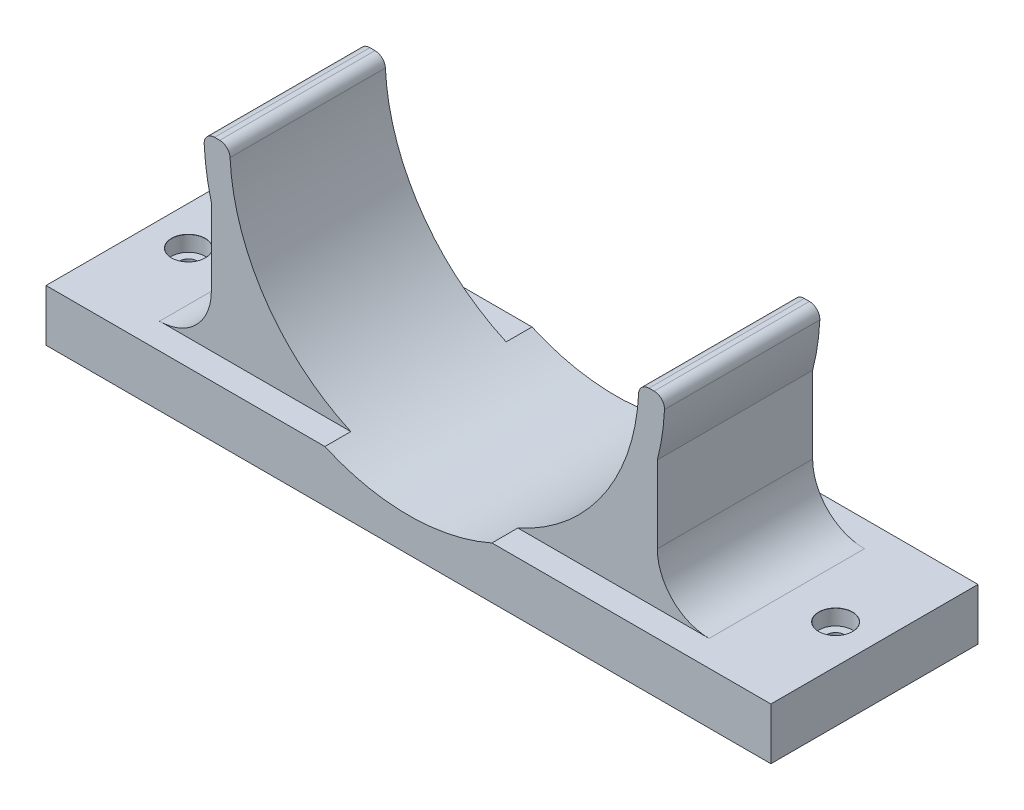
SolidWorks part; units mm, degrees
ref_plane "Front Plane" through (0, 0, 0) normal (0, 0, 1) x (1, 0, 0)
ref_plane "Top Plane" through (0, 0, 0) normal (0, 1, 0) x (1, 0, 0)
ref_plane "Right Plane" through (0, 0, 0) normal (1, 0, 0) x (0, 0, -1)
sketch "Sketch1" plane through (0, 0, 0) normal (0, 0, 1) x (1, 0, 0)
  line L2 (-70, -36.0562) -> (-16.1308, -36.0562)
  line L3 (-70, -36.0562) -> (-70, -46.0562)
  line L4 (-70, -46.0562) -> (70, -46.0562)
  line L5 (70, -36.0562) -> (70, -46.0562)
  line L6 (39.5, 0) -> (44.5, 0)
  line L7 (-70, -41.0562) -> (70, -41.0562) construction
  line L8 (16.1308, -36.0562) -> (70, -36.0562)
  line L9 (-43.0654, -36.0562) -> (-43.0654, -11.2081)
  line L10 (43.0654, -36.0562) -> (43.0654, -11.2081)
  line L12 (-39.5, 0) -> (-44.5, 0)
  line L13 (0, -39.5) -> (0, -46.0562) construction
  line L14 (-44.2182, 5) -> (44.2182, 5) construction
  line L15 (-39.5, 0) -> (39.5, 0) construction
  arc A0 (-39.5, 0) -> (39.5, 0) centre (0, 0) ccw
  arc A1 (-44.5, 0) -> (-26.0807, -36.0562) centre (0, 0) ccw
  arc A2 (26.0807, -36.0562) -> (44.5, 0) centre (0, 0) ccw
  arc A3 (-44.2182, 5) -> (44.2182, 5) centre (0, 0) ccw construction
  dimension "D1" = 140
  dimension "D2" = 10
  dimension "D3" = 5
extrude "Boss-Extrude3" add sketch "Sketch1" along normal blind 20 and the other way blind 20 contours A0 L2 L3 L4 L5 L8 region at (0, -41.2602, 0)
extrude "Boss-Extrude4" add sketch "Sketch1<6>" along normal blind 15 and the other way blind 15 contours L12 A1 L2 A0 | L8 A2 L6 A0 region at (-34.8305, -19.8543, 0) region at (34.8305, -19.8543, 0)
sketch "Sketch1<6>" plane through (0, 0, 0) normal (0, 0, 1) x (1, 0, 0) same geometry as "Sketch1"
extrude "Boss-Extrude5" add sketch "Sketch1<7>" along normal blind 15 and the other way blind 15 contours A2 L8 L10 | A1 L9 L2 region at (-38.0609, -28.9614, 0) region at (38.0609, -28.9614, 0)
sketch "Sketch1<7>" plane through (0, 0, 0) normal (0, 0, 1) x (1, 0, 0) same geometry as "Sketch1"
fillet "Fillet1" radius 10 2 edges at (43.0654, -36.0562, 0) (-43.0654, -36.0562, 0)
sketch "Sketch2" plane through (0, -36.0562, 0) normal (0, 1, 0) x (1, 0, 0)
  line L0 (62.5, 0) -> (70, 0) construction
  line L1 (-70, 20) -> (70, 20)
  line L2 (-70, 20) -> (-70, -20)
  line L3 (-70, -20) -> (70, -20)
  line L4 (70, 20) -> (70, -20)
  line L5 (-70, 0) -> (-62.5, 0) construction
  line L6 (62.5, 20) -> (62.5, -20) construction
  line L7 (-62.5, 20) -> (-62.5, -20) construction
  point P16 (-62.5, 20)
  point P17 (-62.5, 0)
  point P18 (-62.5, -20)
  dimension "D1" = 7.5
hole_wizard "CBORE for M3 SHCS1" positions "Sketch5" profile "Sketch4" counterbore size "M3" standard "ANSI Metric" end condition through all
sketch "Sketch5" plane through (0, -36.0562, 0) normal (0, 1, 0) x (1, 0, 0)
  point P0 (-62.5, 0)
  point P3 (62.5, 0)
sketch "Sketch4" plane through (-62.5, -36.0562, 0) normal (1, 0, 0) x (0, 0, 1)
  line L0 (0, 0) -> (0, 10)
  line L1 (0, 10) -> (1.7, 10)
  line L3 (1.7, 10) -> (1.7, 3)
  line L4 (3.25, 3) -> (1.7, 3)
  line L5 (3.25, 3) -> (3.25, 0.025)
  line L6 (3.25, 0.025) -> (3.275, 0)
  line L7 (3.275, 0) -> (0, 0)
  line L8 (-3.25, 0.025) -> (-3.275, 0) construction
  line L11 (0, -6.35) -> (0, 107.95) construction
  dimension "Thru Hole Dia." = 3.4
  dimension "Thru Hole Depth" = 10
  dimension "C'Bore Dia." = 6.5
  dimension "C'Bore Depth" = 3
  dimension "Near C'Sink Dia." = 6.55
  dimension "Near C'Sink Angle" = 90
fillet "Fillet2" radius 2 4 edges at (-44.5, 0, 0) (-39.5, 0, 0) (44.5, 0, 0) (39.5, 0, 0)
